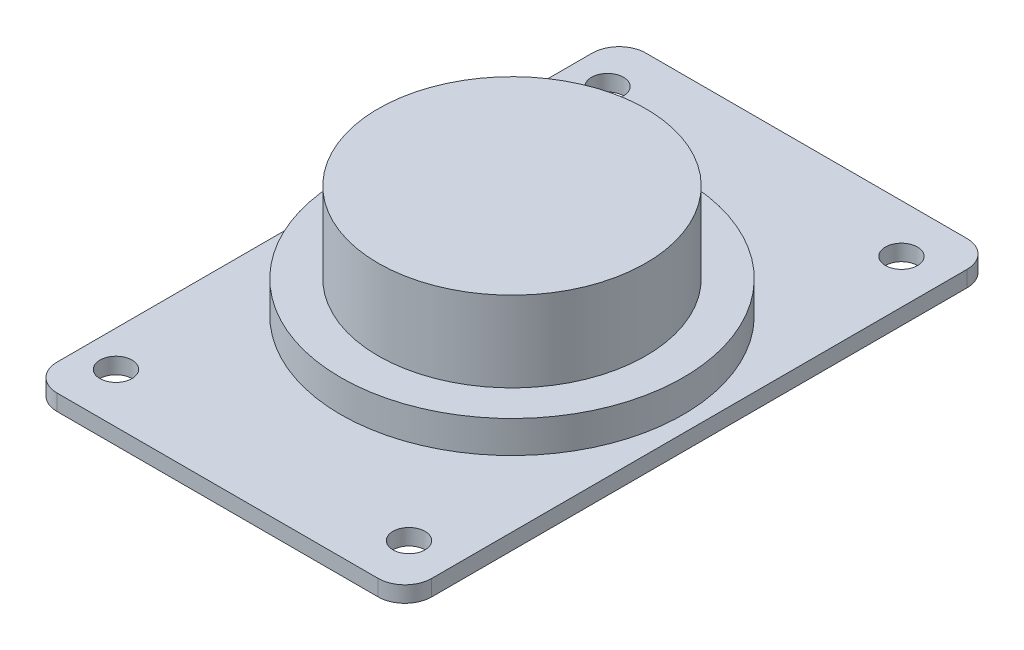
SolidWorks part; units mm, degrees
material "Cast Stainless Steel"
ref_plane "Front Plane" through (0, 0, 0) normal (0, 0, 1) x (1, 0, 0)
ref_plane "Top Plane" through (0, 0, 0) normal (0, 1, 0) x (1, 0, 0)
ref_plane "Right Plane" through (0, 0, 0) normal (1, 0, 0) x (0, 0, -1)
other "Center of Mass"
sketch "Sketch3" plane through (0, 0, 0) normal (0, 1, 0) x (1, 0, 0)
  circle A0 centre (0, 0) radius 25
extrude "Boss-Extrude1" add sketch "Sketch3" against normal blind 15 contours A0
sketch "Sketch4" plane through (0, -15, 0) normal (0, -1, 0) x (1, 0, 0)
  circle A0 centre (0, 0) radius 32
extrude "Boss-Extrude2" add sketch "Sketch4" along normal blind 6
sketch "Sketch6" plane through (0, -21, 0) normal (0, -1, 0) x (1, 0, 0)
  line L1 (35, 0) -> (35, -55)
  line L2 (35, -55) -> (-35, -55)
  line L3 (-35, -55) -> (-35, 55)
  line L4 (-35, 55) -> (35, 55)
  line L5 (35, 55) -> (35, 0)
extrude "Boss-Extrude3" add sketch "Sketch6" along normal blind 3
fillet "Fillet1" radius 5 1 edges at (35, -22.5, 55)
fillet "Fillet2" radius 5 3 edges at (-35, -22.5, 55) (-35, -22.5, -55) (35, -22.5, -55)
sketch "Sketch8" plane through (0, -24, 0) normal (0, -1, 0) x (1, 0, 0)
  circle A0 centre (26.7585, -46) radius 3
  circle A1 centre (-28.159, -46) radius 3
  circle A2 centre (26.7585, 46) radius 3
  circle A3 centre (-28.3209, 45.6631) radius 3
extrude "Cut-Extrude1" cut sketch "Sketch8" against normal blind 3 contours A3 | A2 | A1 | A0
